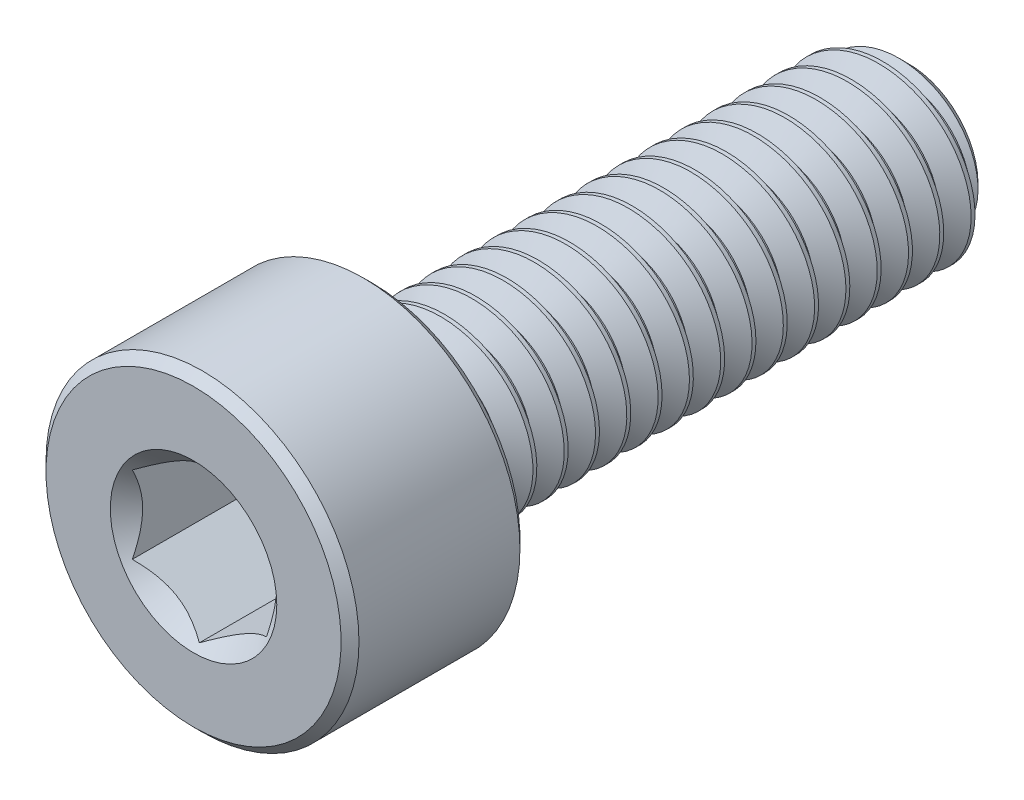
SolidWorks part; units mm, degrees
ref_plane "Front Plane" through (0, 0, 0) normal (0, 0, 1) x (1, 0, 0)
ref_plane "Top Plane" through (0, 0, 0) normal (0, 1, 0) x (1, 0, 0)
ref_plane "Right Plane" through (0, 0, 0) normal (1, 0, 0) x (0, 0, -1)
sketch "Sketch1" plane through (0, 0, 0) normal (1, 0, 0) x (0, 0, -1)
  line L0 (-8, 0) -> (8, 0) construction
  line L1 (8, 0) -> (8, 1.5453) construction
  line L2 (8, 1.5453) -> (7.5453, 2) construction
  line L3 (7.5453, 2) -> (7.475, 2) construction
  line L4 (7.475, 2) -> (-4, 2) construction
  line L5 (-4, 2) -> (-4, 3.5) construction
  line L6 (-4, 3.5) -> (-8, 3.5) construction
  line L7 (-8, 3.5) -> (-8, 0) construction
  line L8 (8, 1.5453) -> (8, 2) construction
  line L9 (7.9563, 2.0758) -> (8.3063, 1.4696) construction
  line L10 (8.3063, 1.4696) -> (8.6562, 2.0758) construction
  line L11 (8.6562, 2.0758) -> (7.9563, 2.0758) construction
  line L12 (8.3063, 2.0758) -> (8.3063, 2) construction
  line L13 (8.3063, 1.4696) -> (8.3063, 1.5453) construction
  line L14 (8.2625, 1.5453) -> (8.35, 1.5453) construction
  line L15 (8, 2) -> (8.6125, 2) construction
  line L16 (7.9781, 2.0379) -> (8.6344, 2.0379) construction
  line L17 (8, 0) -> (8, -2) construction
  line L18 (-4.2, 3.5) -> (-4, 3.3) construction
  line L19 (-7.8, 3.5) -> (-8, 3.3) construction
  line L20 (-4, 2) -> (-4, 0) construction
  line L21 (-4, 1) -> (0, 1) construction
  line L22 (0, 1) -> (4, 1) construction
  line L23 (4, 1) -> (8, 1) construction
  line L24 (0, 1) -> (0, 2) construction
  line L25 (0, 2) -> (0, 3.5) construction
  line L26 (4, 1) -> (4, 3.5) construction
  point P0 (-8, 1.5)
  point P3 (6.25, 2)
  point P4 (0, 0)
  point P18 (4, 2)
  point P22 (8.3063, 1.5453)
  point P24 (7.475, 2)
  point P25 (8.3063, 2)
  point P28 (8.3063, 2.0379)
  point P29 (6.25, -2)
  point P30 (0, 2)
  point P31 (-6, 3.5)
  point P37 (-4.7, 3.5)
  point P38 (-7.7, 3.5)
  point P45 (0, 1)
  point P46 (4, 1)
  dimension "D2" = 0.0875
  dimension "D7" = 0.2
  dimension "D8" = 0.2
  dimension "D9" = 0.2
  dimension "D10" = 0.1
  dimension "D11" = 0.5
  dimension "Drive Size" = 3
  dimension "Head Diameter" = 7
  dimension "Head Height" = 4
  dimension "Thread Pitch" = 0.7
  dimension "Thread Size" = 4
  dimension "Length" = 12
  dimension "D12" = 0.525
  dimension "D4" = 1.75
  dimension "D3" = 45
sketch "Sketch2" plane through (0, 0, 0) normal (1, 0, 0) x (0, 0, -1)
  line L0 (-8, 0) -> (-8, 3.3)
  line L1 (-7.8, 3.5) -> (-4.2, 3.5)
  line L2 (-4, 3.3) -> (-4, 2.2)
  line L4 (7.5453, 2) -> (8, 1.5453)
  line L5 (8, 1.5453) -> (8, 0)
  line L6 (-4, 3.5) -> (-8, 3.5) construction
  line L7 (8, 0) -> (-8, 0)
  line L8 (-7.8, 3.5) -> (-8, 3.3) construction
  line L10 (-7.8, 3.5) -> (-8, 3.3)
  line L14 (-4.2, 3.5) -> (-4, 3.3) construction
  line L16 (-4.2, 3.5) -> (-4, 3.3)
  line L17 (-4, 2) -> (-4, 3.5) construction
  line L19 (-3.8, 2) -> (7.5453, 2)
  line L20 (7.475, 2) -> (-4, 2) construction
  arc A1 (-4, 2.2) -> (-3.8, 2) centre (-3.8, 2.2) ccw
  dimension "D3" = 0.2
revolve "Revolve1" add sketch "Sketch2" angle 360 about L7
sketch "Sketch3" plane through (0, 0, 8) normal (0, 0, 1) x (1, 0, 0)
  line L1 (1.5, -0.866) -> (1.5, 0.866)
  line L2 (1.5, 0.866) -> (0, 1.7321)
  line L3 (0, 1.7321) -> (-1.5, 0.866)
  line L4 (-1.5, 0.866) -> (-1.5, -0.866)
  line L5 (-1.5, -0.866) -> (0, -1.7321)
  line L6 (0, -1.7321) -> (1.5, -0.866)
  circle A0 centre (0, 0) radius 1.5 construction
  circle A1 centre (0, 0) radius 3.5 construction
  circle A2 centre (0, 0) radius 3.5 construction
  circle A3 centre (0, 0) radius 1.7321 construction
  point P13 (0, 0)
  dimension "D1" = 3.4641
extrude "Cut-Extrude1" cut sketch "Sketch3" against normal offset from surface (3 mm away) 1 up to face at (0, 3.3, 4)
sketch "Sketch4" plane through (0, 0, 8) normal (0, 0, 1) x (1, 0, 0)
  circle A0 centre (0, 0) radius 1.862
  dimension "D1" = 3.7239
extrude "Cut-Extrude2" cut sketch "Sketch4" against normal up to vertex (2 mm away) draft 45 up to point (0, 3.5, 6)
sketch "Sketch11" plane through (0, 0, 0) normal (1, 0, 0) x (0, 0, -1)
  line L0 (-8, 0) -> (8, 0) construction
  line L1 (-8, 0) -> (8, 0) construction
  line L2 (-1.75, 0) -> (-1.75, 2) construction
  line L3 (7.475, 2) -> (-4, 2) construction
  line L4 (5.75, 0) -> (5.75, 2) construction
  line L6 (8, 1.5453) -> (8, 2) construction
  point P2 (-1.75, 0)
  point P3 (5.75, 0)
  dimension "D1" = 2.25
  dimension "D2" = 2.25
sketch "Sketch6" plane through (0, 0, -8) normal (0, 0, -1) x (-1, 0, 0)
  circle A0 centre (0, 0) radius 2
curve "Helix/Spiral1" pitch 0.7 height 12.7 turns 18.1429
sketch "Sketch10" plane through (0, 0, 0) normal (1, 0, 0) x (0, 0, -1)
  line L0 (-3.8, -3.5) -> (-3.8, 3.5)
  line L5 (-8, 0) -> (8, 0) construction
  line L6 (-3.8, 2) -> (-3.8, -2) construction
  point P3 (-3.8, 0)
split "Split1" trim tools "Sketch10" bodies to split 106 resulting bodies 114 115
sketch "Sketch7" plane through (0, 0, 0) normal (1, 0, 0) x (0, 0, -1)
  line L0 (7.9781, 2.0379) -> (8.6344, 2.0379)
  line L1 (8.6344, 2.0379) -> (8.35, 1.5453)
  line L2 (8.35, 1.5453) -> (8.2625, 1.5453)
  line L3 (8.2625, 1.5453) -> (7.9781, 2.0379)
sweep "Cut-Sweep1" cut profiles "Sketch7" path "Helix/Spiral1"
sketch "Sketch8" plane through (0, 0, 0) normal (1, 0, 0) x (0, 0, -1)
  line L0 (-4, 0) -> (-4, 2)
  line L1 (-3.8, -2) -> (-3.8, 2) construction
  line L2 (-4, 2) -> (-3.8, 2)
  line L4 (-3.8, 2) -> (-2.6453, 0)
  line L5 (-2.6453, 0) -> (-4, 0)
  line L6 (7.475, 2) -> (-4, 2) construction
  line L7 (-8, 0) -> (8, 0) construction
  dimension "D1" = 60
revolve "Revolve2" add sketch "Sketch8" angle 360 about L5
equation "\"D2@Sketch1\" = \"Thread Pitch@Sketch1\" / 8"
equation "\"D4@Helix/Spiral1\" = \"Thread Pitch@Sketch1\""
equation "\"D7@Sketch1\" = \"Head Height@Sketch1\" * .05"
equation "\"D8@Sketch1\"=\"D7@Sketch1\""
equation "\"D9@Sketch1\"=\"D7@Sketch1\""
equation "\"D10@Sketch1\"=\"D7@Sketch1\"/2"
equation "\"D11@Sketch1\"=\"D10@Sketch1\"*5"
equation "\"D4@Sketch1\"=\"Thread Pitch@Sketch1\"*2.5"
equation "\"D12@Sketch1\"=\"Thread Pitch@Sketch1\"*.75"
equation "\"D3@Helix/Spiral1\"=\"Length@Sketch1\"+\"Thread Pitch@Sketch1\""
equation "\"D3@Sketch2\"=\"Thread Size@Sketch1\"*0.05"
equation "\"D1@Sketch11\"=\"Length@Sketch1\"*0.1875"
equation "\"D2@Sketch11\"=\"D1@Sketch11\""
equation "\"D1@Sketch4\"=\"D1@Sketch3\"*1.075"
